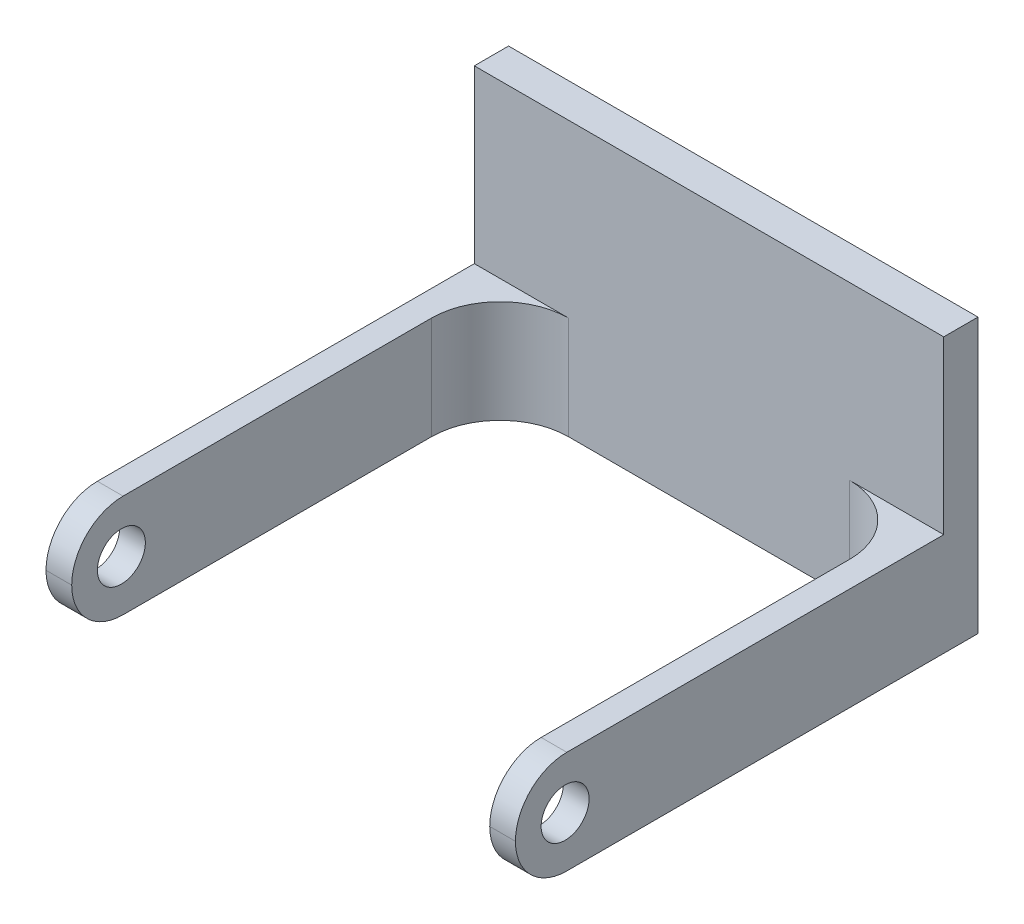
SolidWorks part; units mm, degrees
ref_plane "Front Plane" through (0, 0, 0) normal (0, 0, 1) x (1, 0, 0)
ref_plane "Top Plane" through (0, 0, 0) normal (0, 1, 0) x (1, 0, 0)
ref_plane "Right Plane" through (0, 0, 0) normal (1, 0, 0) x (0, 0, -1)
sketch "Sketch1" plane through (0, 0, 0) normal (0, 0, 1) x (1, 0, 0)
  line L1 (-13.7, -3) -> (13.7, -3)
  line L2 (-13.7, -3) -> (-13.7, 3)
  line L3 (-13.7, 3) -> (13.7, 3)
  line L4 (13.7, -3) -> (13.7, 3)
  line L5 (-13.7, -3) -> (13.7, 3) construction
  line L6 (-13.7, 3) -> (13.7, -3) construction
  point P0 (0, 0)
  dimension "D1" = 27.4
  dimension "D2" = 6
extrude "Boss-Extrude1" add sketch "Sketch1" along normal blind 2
sketch "Sketch2" plane through (0, 0, 2) normal (0, 0, 1) x (1, 0, 0)
  line L0 (-13.7, -3) -> (13.7, -3) construction
  line L1 (-13.7, 3) -> (-12.2, 3)
  line L2 (-13.7, 3) -> (-13.7, -3)
  line L3 (-13.7, -3) -> (-12.2, -3)
  line L4 (-12.2, 3) -> (-12.2, -3)
  line L6 (13.7, 3) -> (12.2, 3)
  line L7 (13.7, 3) -> (13.7, -3)
  line L8 (13.7, -3) -> (12.2, -3)
  line L9 (12.2, 3) -> (12.2, -3)
  dimension "D1" = 1.5
  dimension "D2" = 1.5
extrude "Boss-Extrude2" add sketch "Sketch2" along normal blind 25
sketch "Sketch3" plane through (13.7, 0, 0) normal (1, 0, 0) x (0, 0, -1)
  line L0 (-27, -3) -> (-27, 3) construction
  circle A0 centre (-24.1, 0) radius 1.4
  dimension "D1" = 2.8
  dimension "D2" = 2.9
extrude "Cut-Extrude1" cut sketch "Sketch3" against normal through all
fillet "Fillet1" radius 3 4 edges at (-12.95, -3, 27) (12.95, -3, 27) (-12.95, 3, 27) (12.95, 3, 27)
sketch "Sketch4" plane through (0, 3, 0) normal (0, 1, 0) x (1, 0, 0)
  line L0 (13.7, -24) -> (13.7, 0) construction
  line L1 (-13.7, 0) -> (13.7, 0)
  line L2 (-13.7, 0) -> (-13.7, -2)
  line L3 (-13.7, -2) -> (13.7, -2)
  line L4 (13.7, 0) -> (13.7, -2)
  dimension "D1" = 2
extrude "Boss-Extrude3" add sketch "Sketch4" along normal blind 10
fillet "Fillet2" radius 4 2 edges at (12.2, 0, 2)
